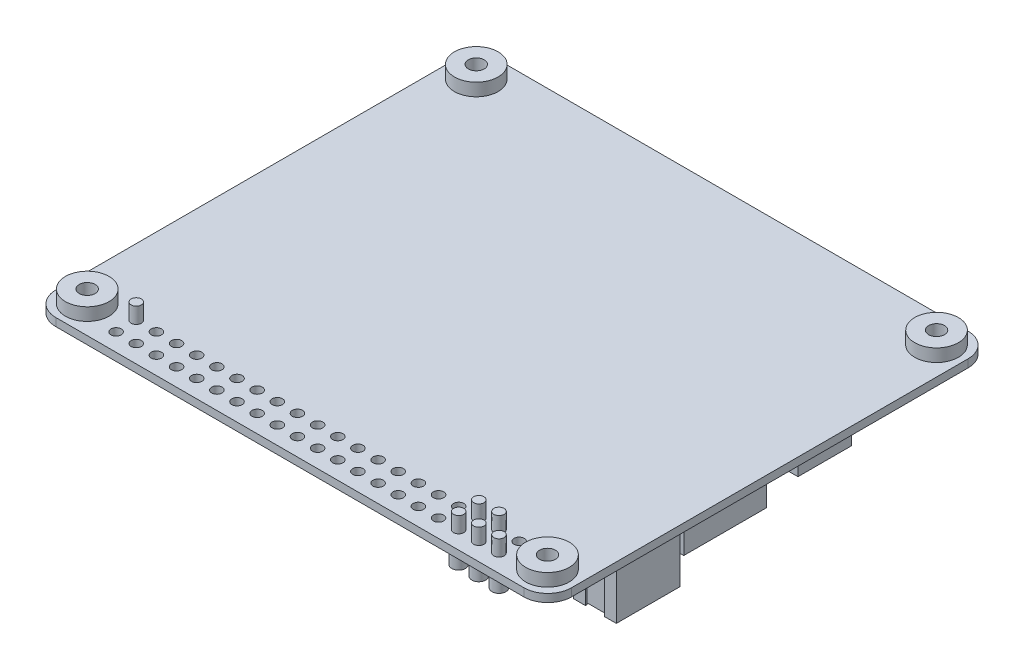
SolidWorks part; units mm, degrees
ref_plane "前视基准面" through (0, 0, 0) normal (0, 0, 1) x (1, 0, 0)
ref_plane "上视基准面" through (0, 0, 0) normal (0, 1, 0) x (1, 0, 0)
ref_plane "右视基准面" through (0, 0, 0) normal (1, 0, 0) x (0, 0, -1)
sketch "草图1" plane through (0, 0, 0) normal (0, 1, 0) x (1, 0, 0)
  line L1 (32.5, -28) -> (-32.5, -28)
  line L2 (32.5, -28) -> (32.5, 28)
  line L3 (32.5, 28) -> (-32.5, 28)
  line L4 (-32.5, -28) -> (-32.5, 28)
  line L5 (32.5, -28) -> (-32.5, 28) construction
  line L6 (32.5, 28) -> (-32.5, -28) construction
  point P0 (0, 0)
  dimension "D1" = 56
  dimension "D2" = 65
extrude "凸台-拉伸1" add sketch "草图1" along normal blind 1
fillet "圆角1" radius 3 4 edges at (32.5, 0.5, -28) (32.5, 0.5, 28) (-32.5, 0.5, 28) (-32.5, 0.5, -28)
sketch "草图2" plane through (0, 1, 0) normal (0, 1, 0) x (1, 0, 0)
  circle A0 centre (-29.0307, 24.5287) radius 2.75
  circle A1 centre (28.9808, 24.5287) radius 2.75
  circle A2 centre (-29.0307, -24.5065) radius 2.75
  circle A3 centre (28.9808, -24.5065) radius 2.75
  dimension "D1" = 5.5
extrude "凸台-拉伸2" add sketch "草图2" along normal blind 1.6
sketch "草图3" plane through (0, 2.6, 0) normal (0, 1, 0) x (1, 0, 0)
  circle A0 centre (-29.0307, 24.5287) radius 1
  circle A1 centre (28.9808, 24.5287) radius 1
  circle A2 centre (-29.0307, -24.5065) radius 1
  circle A3 centre (28.9808, -24.5065) radius 1
  dimension "D1" = 2
extrude "切除-拉伸1" cut sketch "草图3" against normal up to next
sketch "草图4" plane through (0, 0, 0) normal (0, -1, 0) x (1, 0, 0)
  line L0 (29.5, -28) -> (-29.5, -28) construction
  line L1 (25.5, -28) -> (16.5, -28)
  line L2 (25.5, -28) -> (25.5, -20.6)
  line L3 (25.5, -20.6) -> (16.5, -20.6)
  line L4 (16.5, -28) -> (16.5, -20.6)
  line L5 (32.5, 25) -> (32.5, -25) construction
  dimension "D1" = 7.4
  dimension "D2" = 9
  dimension "D3" = 7
extrude "凸台-拉伸3" add sketch "草图4" along normal blind 3.2
sketch "草图5" plane through (0, 0, -28) normal (0, 0, -1) x (-1, 0, 0)
  line L0 (-29.5, 0) -> (-25.5, 0) construction
  line L1 (-16.5, -3.2) -> (-25.5, -3.2)
  line L2 (-16.5, -3.2) -> (-16.5, 0)
  line L3 (-16.5, 0) -> (-25.5, 0)
  line L4 (-25.5, -3.2) -> (-25.5, 0)
  line L5 (-25.5, -3.2) -> (-25.5, 0) construction
extrude "凸台-拉伸4" add sketch "草图5" along normal blind 1
fillet "圆角3" radius 1 4 edges at (25.5, 0, -28.5) (25.5, -3.2, -24.8) (16.5, -3.2, -24.8) (16.5, 0, -28.5)
sketch "草图6" plane through (0, 0, 0) normal (0, -1, 0) x (1, 0, 0)
  line L0 (-32.5, -25) -> (-32.5, 25) construction
  circle A0 centre (-17.5, 0) radius 7
  dimension "D1" = 14
  dimension "D2" = 15
extrude "凸台-拉伸5" add sketch "草图6" along normal blind 2
sketch "草图8" plane through (0, 0, 0) normal (0, -1, 0) x (1, 0, 0)
  circle A0 centre (28.9808, 24.5065) radius 2
  circle A1 centre (28.9808, -24.5287) radius 2
  circle A2 centre (-29.0307, -24.5287) radius 2
  circle A3 centre (-29.0307, 24.5065) radius 2
  dimension "D1" = 4
extrude "凸台-拉伸6" add sketch "草图8" along normal blind 0.5
sketch "草图9" plane through (0, 0, 0) normal (0, 1, 0) x (1, 0, 0)
  circle A0 centre (-29.0307, 24.5287) radius 1
  circle A1 centre (28.9808, 24.5287) radius 1
  circle A2 centre (-29.0307, -24.5065) radius 1
  circle A3 centre (28.9808, -24.5065) radius 1
  circle A4 centre (28.9808, -24.5065) radius 2 construction
  circle A5 centre (28.9808, 24.5287) radius 2 construction
  circle A6 centre (-29.0307, -24.5065) radius 2 construction
  circle A7 centre (-29.0307, 24.5287) radius 2 construction
extrude "切除-拉伸2" cut sketch "草图9" against normal up to next
sketch "草图10" plane through (0, 0, -29) normal (0, 0, -1) x (-1, 0, 0)
  line L8 (-17.5, -0.2) -> (-24.5, -0.2)
  line L9 (-25.3, -1) -> (-25.3, -2.2)
  line L10 (-24.5, -3) -> (-17.5, -3)
  line L11 (-16.7, -2.2) -> (-16.7, -1)
  line L12 (-17.5, -0.2) -> (-24.5, -0.2)
  line L13 (-25.3, -1) -> (-25.3, -2.2)
  line L14 (-24.5, -3) -> (-17.5, -3)
  line L15 (-16.7, -2.2) -> (-16.7, -1)
  arc A8 (-24.5, -0.2) -> (-25.3, -1) centre (-24.5, -1) ccw
  arc A9 (-25.3, -2.2) -> (-24.5, -3) centre (-24.5, -2.2) ccw
  arc A10 (-17.5, -3) -> (-16.7, -2.2) centre (-17.5, -2.2) ccw
  arc A11 (-16.7, -1) -> (-17.5, -0.2) centre (-17.5, -1) ccw
  arc A12 (-24.5, -0.2) -> (-25.3, -1) centre (-24.5, -1) ccw
  arc A13 (-25.3, -2.2) -> (-24.5, -3) centre (-24.5, -2.2) ccw
  arc A14 (-17.5, -3) -> (-16.7, -2.2) centre (-17.5, -2.2) ccw
  arc A15 (-16.7, -1) -> (-17.5, -0.2) centre (-17.5, -1) ccw
  dimension "D1" = 0.2
extrude "切除-拉伸3" cut sketch "草图10" against normal blind 8
sketch "草图12" plane through (0, 0, 0) normal (0, -1, 0) x (1, 0, 0)
  line L0 (16.5, -28) -> (-29.5, -28) construction
  line L1 (-16.6, -28) -> (-23.9, -28)
  line L2 (-16.6, -28) -> (-16.6, -22.7)
  line L3 (-16.6, -22.7) -> (-23.9, -22.7)
  line L4 (-23.9, -28) -> (-23.9, -22.7)
  line L5 (-32.5, -25) -> (-32.5, 25) construction
  dimension "D1" = 7.3
  dimension "D2" = 8.6
  dimension "D3" = 5.3
extrude "凸台-拉伸8" add sketch "草图12" along normal blind 2.4
sketch "草图13" plane through (0, 0, -28) normal (0, 0, -1) x (-1, 0, 0)
  line L1 (23.9, -2.4) -> (16.6, -2.4)
  line L2 (23.9, -2.4) -> (23.9, 0)
  line L3 (23.9, 0) -> (16.6, 0)
  line L4 (16.6, -2.4) -> (16.6, 0)
extrude "凸台-拉伸9" add sketch "草图13" along normal up to surface (1 mm away) up to face at (21, -1.6, -29)
chamfer "倒角1" distance 0.4 angle 45 2 edges at (-16.6, -2.4, -25.85) (-23.9, -2.4, -25.85)
chamfer "倒角2" distance 1 angle 45 2 edges at (-16.6, 0, -28.5) (-23.9, 0, -28.5)
sketch "草图14" plane through (0, 0, -29) normal (0, 0, -1) x (-1, 0, 0)
  line L16 (22.8172, -0.2) -> (17.6828, -0.2)
  line L17 (17.6828, -0.2) -> (16.8, -1.0828)
  line L18 (16.8, -1.0828) -> (16.8, -1.9172)
  line L19 (16.8, -1.9172) -> (17.0828, -2.2)
  line L20 (17.0828, -2.2) -> (23.4172, -2.2)
  line L21 (23.4172, -2.2) -> (23.7, -1.9172)
  line L22 (23.7, -1.9172) -> (23.7, -1.0828)
  line L23 (23.7, -1.0828) -> (22.8172, -0.2)
  line L24 (22.8172, -0.2) -> (17.6828, -0.2)
  line L25 (17.6828, -0.2) -> (16.8, -1.0828)
  line L26 (16.8, -1.0828) -> (16.8, -1.9172)
  line L27 (16.8, -1.9172) -> (17.0828, -2.2)
  line L28 (17.0828, -2.2) -> (23.4172, -2.2)
  line L29 (23.4172, -2.2) -> (23.7, -1.9172)
  line L30 (23.7, -1.9172) -> (23.7, -1.0828)
  line L31 (23.7, -1.0828) -> (22.8172, -0.2)
  dimension "D1" = 0.2
extrude "切除-拉伸4" cut sketch "草图14" against normal blind 2.4
sketch "草图17" plane through (0, 0, -28) normal (0, 0, -1) x (-1, 0, 0)
  line L0 (23.9, -1) -> (23.9, 0)
  line L1 (23.9, 0) -> (22.9, 0)
  line L2 (22.9, 0) -> (23.9, -1)
  line L3 (16.6, 0) -> (17.6, 0)
  line L4 (17.6, 0) -> (16.6, -1)
  line L5 (16.6, -1) -> (16.6, 0) construction
  line L6 (16.6, -1) -> (16.6, 0)
extrude "切除-拉伸5" cut sketch "草图17" against normal up to surface (5.3 mm away) up to face at (-20.25, -1.4667, -22.7)
fillet "圆角4" radius 0.2 1 edges at (-17.5, -2, -7)
sketch "草图19" plane through (0, 0, 0) normal (0, -1, 0) x (1, 0, 0)
  line L0 (32.5, 25) -> (32.5, -25) construction
  line L1 (32, 18.85) -> (26.6, 18.85)
  line L2 (32, 18.85) -> (32, 10.85)
  line L3 (32, 10.85) -> (26.6, 10.85)
  line L4 (26.6, 18.85) -> (26.6, 10.85)
  line L5 (-29.5, 28) -> (29.5, 28) construction
  dimension "D1" = 8
  dimension "D2" = 5.4
  dimension "D3" = 0.5
  dimension "D4" = 9.15
extrude "凸台-拉伸13" add sketch "草图19" along normal blind 6.22
sketch "草图20" plane through (0, -6.22, 0) normal (0, -1, 0) x (1, 0, 0)
  line L0 (30.5, 18.85) -> (30.5, 18.65)
  line L1 (32, 18.85) -> (26.6, 18.85) construction
  line L2 (30.5, 18.65) -> (31.3599, 18.65)
  line L3 (31.3599, 18.65) -> (31.3599, 18.45)
  line L4 (31.3599, 18.45) -> (26.9378, 18.45)
  line L5 (26.9378, 18.45) -> (26.9378, 18.65)
  line L6 (26.9378, 18.65) -> (28.1, 18.65)
  line L7 (28.1, 18.65) -> (28.1, 18.85)
  line L8 (32, 18.85) -> (26.6, 18.85) construction
  line L9 (28.1, 18.85) -> (30.5, 18.85)
  line L10 (30.5, 10.85) -> (30.5, 11.05)
  line L11 (26.6, 10.85) -> (32, 10.85) construction
  line L12 (30.5, 11.05) -> (31.3599, 11.05)
  line L13 (31.3599, 11.05) -> (31.3599, 11.25)
  line L14 (31.3599, 11.25) -> (26.9378, 11.25)
  line L15 (26.9378, 11.25) -> (26.9378, 11.05)
  line L16 (26.9378, 11.05) -> (28.1, 11.05)
  line L17 (28.1, 11.05) -> (28.1, 10.85)
  line L18 (28.1, 10.85) -> (30.5, 10.85)
  line L19 (32, 10.85) -> (32, 18.85) construction
  line L20 (26.6, 18.85) -> (26.6, 10.85) construction
  dimension "D1" = 0.2
  dimension "D2" = 0.2
  dimension "D3" = 0.2
  dimension "D4" = 1.5
  dimension "D5" = 1.5
extrude "切除-拉伸6" cut sketch "草图20" against normal blind 6.22
sketch "草图21" plane through (0, -6.22, 0) normal (0, -1, 0) x (1, 0, 0)
  line L1 (31.3599, 18.0753) -> (26.9378, 18.0753)
  line L2 (31.3599, 18.0753) -> (31.3599, 11.6247)
  line L3 (31.3599, 11.6247) -> (26.9378, 11.6247)
  line L4 (26.9378, 18.0753) -> (26.9378, 11.6247)
  line L5 (31.3599, 18.0753) -> (26.9378, 11.6247) construction
  line L6 (31.3599, 11.6247) -> (26.9378, 18.0753) construction
  point P0 (29.1489, 14.85)
extrude "切除-拉伸7" cut sketch "草图21" against normal blind 5
sketch "草图22" plane through (0, -1.22, 0) normal (0, -1, 0) x (1, 0, 0)
  line L1 (29.5742, 16.0721) -> (29.0742, 16.0721)
  line L2 (29.5742, 16.0721) -> (29.5742, 15.5721)
  line L3 (29.5742, 15.5721) -> (29.0742, 15.5721)
  line L4 (29.0742, 16.0721) -> (29.0742, 15.5721)
  line L5 (29.5742, 16.0721) -> (29.0742, 15.5721) construction
  line L6 (29.5742, 15.5721) -> (29.0742, 16.0721) construction
  line L7 (29.5566, 14.331) -> (29.0566, 14.331)
  line L8 (29.5566, 14.331) -> (29.5566, 13.831)
  line L9 (29.5566, 13.831) -> (29.0566, 13.831)
  line L10 (29.0566, 14.331) -> (29.0566, 13.831)
  line L11 (29.5566, 14.331) -> (29.0566, 13.831) construction
  line L12 (29.5566, 13.831) -> (29.0566, 14.331) construction
  point P0 (29.3242, 15.8221)
  point P5 (29.3066, 14.081)
  dimension "D1" = 0.5
extrude "凸台-拉伸14" add sketch "草图22" along normal blind 5
chamfer "倒角3" distance 0.1 angle 45 8 edges at (29.3066, -6.22, 14.331) (29.5566, -6.22, 14.081) (29.3066, -6.22, 13.831) (29.0566, -6.22, 14.081) (29.3242, -6.22, 16.0721) (29.5742, -6.22, 15.8221) (29.3242, -6.22, 15.5721) (29.0742, -6.22, 15.8221)
sketch "草图26" plane through (0, 0, 0) normal (0, -1, 0) x (1, 0, 0)
  circle A0 centre (24.13, 25.77) radius 0.65
  circle A40 centre (21.59, 25.77) radius 0.65
  circle A41 centre (19.05, 25.77) radius 0.65
  circle A42 centre (16.51, 25.77) radius 0.65
  circle A43 centre (13.97, 25.77) radius 0.65
  circle A44 centre (11.43, 25.77) radius 0.65
  circle A45 centre (8.89, 25.77) radius 0.65
  circle A46 centre (6.35, 25.77) radius 0.65
  circle A47 centre (3.81, 25.77) radius 0.65
  circle A48 centre (1.27, 25.77) radius 0.65
  circle A49 centre (-1.27, 25.77) radius 0.65
  circle A50 centre (-3.81, 25.77) radius 0.65
  circle A51 centre (-6.35, 25.77) radius 0.65
  circle A52 centre (-8.89, 25.77) radius 0.65
  circle A53 centre (-11.43, 25.77) radius 0.65
  circle A54 centre (-13.97, 25.77) radius 0.65
  circle A55 centre (-16.51, 25.77) radius 0.65
  circle A56 centre (-19.05, 25.77) radius 0.65
  circle A57 centre (-21.59, 25.77) radius 0.65
  circle A58 centre (-24.13, 25.77) radius 0.65
  circle A59 centre (21.59, 23.23) radius 0.65
  circle A60 centre (19.05, 23.23) radius 0.65
  circle A61 centre (16.51, 23.23) radius 0.65
  circle A62 centre (13.97, 23.23) radius 0.65
  circle A63 centre (11.43, 23.23) radius 0.65
  circle A64 centre (8.89, 23.23) radius 0.65
  circle A65 centre (6.35, 23.23) radius 0.65
  circle A66 centre (3.81, 23.23) radius 0.65
  circle A67 centre (1.27, 23.23) radius 0.65
  circle A68 centre (-1.27, 23.23) radius 0.65
  circle A69 centre (-3.81, 23.23) radius 0.65
  circle A70 centre (-6.35, 23.23) radius 0.65
  circle A71 centre (-8.89, 23.23) radius 0.65
  circle A72 centre (-11.43, 23.23) radius 0.65
  circle A73 centre (-13.97, 23.23) radius 0.65
  circle A74 centre (-16.51, 23.23) radius 0.65
  circle A75 centre (-19.05, 23.23) radius 0.65
  circle A76 centre (-21.59, 23.23) radius 0.65
  circle A77 centre (-24.13, 23.23) radius 0.65
  circle A78 centre (24.13, 23.23) radius 0.65
  dimension "D1" = 1.3
  dimension "D2" = 20
  dimension "D3" = 2
extrude "切除-拉伸8" cut sketch "草图26" against normal up to surface (1 mm away) up to face at (28.9808, 1, 27.2565)
sketch "草图27" plane through (0, 0, 0) normal (0, -1, 0) x (1, 0, 0)
  circle A0 centre (24.13, 25.77) radius 1.15
  circle A1 centre (21.59, 25.77) radius 1.15
  circle A2 centre (21.59, 23.23) radius 1.15
  circle A3 centre (19.05, 25.77) radius 1.15
  circle A4 centre (19.05, 23.23) radius 1.15
  circle A5 centre (13.97, 23.23) radius 1.15
  circle A6 centre (21.59, 25.77) radius 0.65 construction
  dimension "D1" = 2.3
extrude "凸台-拉伸18" add sketch "草图27" along normal blind 0.8
sketch "草图28" plane through (0, -0.8, 0) normal (0, -1, 0) x (-1, 0, 0)
  circle A0 centre (-24.13, -25.77) radius 0.875
  circle A1 centre (-21.59, -25.77) radius 0.875
  circle A2 centre (-19.05, -23.23) radius 0.875
  circle A3 centre (-21.59, -23.23) radius 0.875
  circle A4 centre (-19.05, -25.77) radius 0.875
  circle A5 centre (-13.97, -23.23) radius 0.875
  dimension "D1" = 1.75
extrude "凸台-拉伸19" add sketch "草图28" along normal blind 2
sketch "草图29" plane through (0, 0, 0) normal (0, 1, 0) x (1, 0, 0)
  circle A0 centre (19.05, -23.23) radius 0.65 construction
  circle A1 centre (19.05, -25.77) radius 0.65 construction
  circle A2 centre (21.59, -23.23) radius 0.65 construction
  circle A4 centre (24.13, -25.77) radius 0.65 construction
  circle A5 centre (-24.13, -23.23) radius 0.65 construction
  circle A6 centre (19.05, -23.23) radius 0.65
  circle A7 centre (19.05, -25.77) radius 0.65
  circle A8 centre (21.59, -23.23) radius 0.65
  circle A9 centre (21.59, -25.77) radius 0.65
  circle A10 centre (24.13, -25.77) radius 0.65
  circle A11 centre (-24.13, -23.23) radius 0.65
  circle A12 centre (21.59, -25.77) radius 0.65 construction
extrude "凸台-拉伸20" add sketch "草图29" along normal blind 3
sketch "草图30" plane through (0, 0, -28) normal (0, 0, -1) x (-1, 0, 0)
  line L0 (-16.5, 0) -> (-17.5, 0)
  line L1 (-16.5, 0) -> (-16.5, -1) construction
  line L2 (-16.5, 0) -> (-16.5, -1)
  line L3 (-25.5, 0) -> (-24.5, 0)
  line L4 (-25.5, -1) -> (-25.5, 0) construction
  line L5 (-25.5, -1) -> (-25.5, 0)
  arc A0 (-16.5, -1) -> (-17.5, 0) centre (-17.5, -1) ccw construction
  arc A1 (-16.5, -1) -> (-17.5, 0) centre (-17.5, -1) ccw
  arc A2 (-24.5, 0) -> (-25.5, -1) centre (-24.5, -1) ccw construction
  arc A3 (-24.5, 0) -> (-25.5, -1) centre (-24.5, -1) ccw
extrude "切除-拉伸9" cut sketch "草图30" against normal up to next
sketch "草图31" plane through (0, 0, 0) normal (0, -1, 0) x (1, 0, 0)
  line L0 (-269.1222, 141.019) -> (182.8778, 141.019) construction
  line L1 (24.5, -20.6) -> (17.5, -20.6) construction
  line L2 (31.459, 9.8102) -> (19.8345, 9.8102)
  line L3 (31.459, 9.8102) -> (31.459, -0.6109)
  line L4 (31.459, -0.6109) -> (19.8345, -0.6109)
  line L5 (19.8345, 9.8102) -> (19.8345, -0.6109)
  line L6 (31.459, -1.1785) -> (28.1669, -1.1785)
  line L7 (31.459, -1.1785) -> (31.459, -4.516)
  line L8 (31.459, -4.516) -> (28.1669, -4.516)
  line L9 (28.1669, -1.1785) -> (28.1669, -4.516)
  line L10 (27.1452, -1.4056) -> (22.332, -1.4056)
  line L11 (27.1452, -1.4056) -> (27.1452, -4.1981)
  line L12 (27.1452, -4.1981) -> (22.332, -4.1981)
  line L13 (22.332, -1.4056) -> (22.332, -4.1981)
  line L14 (31.0503, -4.9928) -> (23.558, -4.9928)
  line L15 (31.0503, -4.9928) -> (31.0503, -11.7586)
  line L16 (31.0503, -11.7586) -> (23.558, -11.7586)
  line L17 (23.558, -4.9928) -> (23.558, -11.7586)
  line L18 (31.459, -13.2884) -> (30.0812, -13.2884)
  line L19 (31.459, -13.2884) -> (31.459, -15.1195)
  line L20 (31.459, -15.1195) -> (30.0812, -15.1195)
  line L21 (30.0812, -13.2884) -> (30.0812, -15.1195)
  line L22 (29.3946, -12.2203) -> (27.6398, -12.2203)
  line L23 (29.3946, -12.2203) -> (29.3946, -13.0596)
  line L24 (29.3946, -13.0596) -> (27.6398, -13.0596)
  line L25 (27.6398, -12.2203) -> (27.6398, -13.0596)
  line L26 (25.1221, -19.2775) -> (23.024, -19.2775)
  line L27 (25.1221, -19.2775) -> (25.1221, -20.6)
  line L28 (25.1221, -20.6) -> (23.024, -20.6)
  line L29 (23.024, -19.2775) -> (23.024, -20.6)
  line L30 (24.5, -20.6) -> (17.5, -20.6) construction
  line L31 (21.8033, -19.2775) -> (20.7352, -19.2775)
  line L32 (21.8033, -19.2775) -> (21.8033, -20.6)
  line L33 (21.8033, -20.6) -> (20.7352, -20.6)
  line L34 (20.7352, -19.2775) -> (20.7352, -20.6)
  line L35 (-4.9095, -24.5987) -> (-6.2095, -24.5987)
  line L36 (20.2393, -19.2775) -> (19.2474, -19.2775)
  line L37 (20.2393, -19.2775) -> (20.2393, -20.6)
  line L38 (20.2393, -20.6) -> (19.2474, -20.6)
  line L39 (19.2474, -19.2775) -> (19.2474, -20.6)
  line L40 (25.1221, -17.065) -> (23.024, -17.065)
  line L41 (25.1221, -17.065) -> (25.1221, -18.5146)
  line L42 (25.1221, -18.5146) -> (23.024, -18.5146)
  line L43 (23.024, -17.065) -> (23.024, -18.5146)
  line L44 (21.2692, -13.0596) -> (18.103, -13.0596)
  line L45 (21.2692, -13.0596) -> (21.2692, -16.3402)
  line L46 (21.2692, -16.3402) -> (18.103, -16.3402)
  line L47 (18.103, -13.0596) -> (18.103, -16.3402)
  line L48 (19.2474, -0.6109) -> (18.4047, -0.6109)
  line L49 (19.2474, -0.6109) -> (19.2474, -2.216)
  line L50 (19.2474, -2.216) -> (18.4047, -2.216)
  line L51 (18.4047, -0.6109) -> (18.4047, -2.216)
  line L52 (13.1588, -24.973) -> (8.3931, -24.973)
  line L53 (13.1588, -24.973) -> (13.1588, -27.3005)
  line L54 (13.1588, -27.3005) -> (8.3931, -27.3005)
  line L55 (8.3931, -24.973) -> (8.3931, -27.3005)
  line L56 (4.6988, -24.973) -> (0, -24.973)
  line L57 (4.6988, -24.973) -> (4.6988, -27.3005)
  line L58 (4.6988, -27.3005) -> (0, -27.3005)
  line L59 (0, -24.973) -> (0, -27.3005)
  line L60 (8.3931, 15.9758) -> (4.9221, 15.9758)
  line L61 (8.3931, 15.9758) -> (8.3931, 13.2491)
  line L62 (8.3931, 13.2491) -> (4.9221, 13.2491)
  line L63 (4.9221, 15.9758) -> (4.9221, 13.2491)
  line L64 (8.3931, 11.7221) -> (4.9221, 11.7221)
  line L65 (8.3931, 11.7221) -> (8.3931, 9.0318)
  line L66 (8.3931, 9.0318) -> (4.9221, 9.0318)
  line L67 (4.9221, 11.7221) -> (4.9221, 9.0318)
  line L68 (9.6847, 6.3051) -> (5.9037, 6.3051)
  line L69 (9.6847, 6.3051) -> (9.6847, 1.4698)
  line L70 (9.6847, 1.4698) -> (5.9037, 1.4698)
  line L71 (5.9037, 6.3051) -> (5.9037, 1.4698)
  line L80 (-1.5572, -24.1659) -> (-3.3676, -24.1659)
  line L81 (-1.5572, -24.1659) -> (-1.5572, -27.3005)
  line L82 (-1.5572, -27.3005) -> (-3.3676, -27.3005)
  line L83 (-3.3676, -24.1659) -> (-3.3676, -27.3005)
  line L88 (-4.9095, -24.5987) -> (-4.9095, -26.7453)
  line L89 (-4.9095, -26.7453) -> (-6.2095, -26.7453)
  line L90 (-6.2095, -24.5987) -> (-6.2095, -26.7453)
  line L92 (-7.0018, -24.5987) -> (-8.3018, -24.5987)
  line L93 (-7.0018, -24.5987) -> (-7.0018, -26.7453)
  line L94 (-7.0018, -26.7453) -> (-8.3018, -26.7453)
  line L95 (-8.3018, -24.5987) -> (-8.3018, -26.7453)
  line L96 (-9.1473, -24.5987) -> (-10.4473, -24.5987)
  line L97 (-9.1473, -24.5987) -> (-9.1473, -26.7453)
  line L98 (-9.1473, -26.7453) -> (-10.4473, -26.7453)
  line L99 (-10.4473, -24.5987) -> (-10.4473, -26.7453)
  line L100 (-11.2125, -24.5987) -> (-12.5125, -24.5987)
  line L101 (-11.2125, -24.5987) -> (-11.2125, -26.7453)
  line L102 (-11.2125, -26.7453) -> (-12.5125, -26.7453)
  line L103 (-12.5125, -24.5987) -> (-12.5125, -26.7453)
  line L104 (-13.2578, -24.5987) -> (-14.5578, -24.5987)
  line L105 (-13.2578, -24.5987) -> (-13.2578, -26.7453)
  line L106 (-13.2578, -26.7453) -> (-14.5578, -26.7453)
  line L107 (-14.5578, -24.5987) -> (-14.5578, -26.7453)
  line L108 (0.6545, -17.8156) -> (-0.8398, -17.8156)
  line L109 (0.6545, -17.8156) -> (0.6545, -19.6835)
  line L110 (0.6545, -19.6835) -> (-0.8398, -19.6835)
  line L111 (-0.8398, -17.8156) -> (-0.8398, -19.6835)
  line L112 (-9.9754, -18.0873) -> (-11.6734, -18.0873)
  line L113 (-9.9754, -18.0873) -> (-9.9754, -18.9703)
  line L114 (-9.9754, -18.9703) -> (-11.6734, -18.9703)
  line L115 (-11.6734, -18.0873) -> (-11.6734, -18.9703)
  line L116 (-1.2233, 3.594) -> (-2.668, 3.594)
  line L117 (-1.2233, 3.594) -> (-1.2233, 1.8282)
  line L118 (-1.2233, 1.8282) -> (-2.668, 1.8282)
  line L119 (-2.668, 3.594) -> (-2.668, 1.8282)
  line L120 (-2.2552, -2.7581) -> (-3.1725, -2.7581)
  line L121 (-2.2552, -2.7581) -> (-2.2552, -4.516)
  line L122 (-2.2552, -4.516) -> (-3.1725, -4.516)
  line L123 (-3.1725, -2.7581) -> (-3.1725, -4.516)
  line L124 (-4.6401, -2.7581) -> (-5.5344, -2.7581)
  line L125 (-4.6401, -2.7581) -> (-4.6401, -4.516)
  line L126 (-4.6401, -4.516) -> (-5.5344, -4.516)
  line L127 (-5.5344, -2.7581) -> (-5.5344, -4.516)
  line L128 (-6.2095, -3.8955) -> (-7.2269, -3.8955)
  line L129 (-6.2095, -3.8955) -> (-6.2095, -5.7277)
  line L130 (-6.2095, -5.7277) -> (-7.2269, -5.7277)
  line L131 (-7.2269, -3.8955) -> (-7.2269, -5.7277)
  line L132 (-7.6341, -3.8955) -> (-8.5039, -3.8955)
  line L133 (-7.6341, -3.8955) -> (-7.6341, -5.7277)
  line L134 (-7.6341, -5.7277) -> (-8.5039, -5.7277)
  line L135 (-8.5039, -3.8955) -> (-8.5039, -5.7277)
  line L136 (-8.8925, -3.8955) -> (-9.8179, -3.8955)
  line L137 (-8.8925, -3.8955) -> (-8.8925, -5.7277)
  line L138 (-8.8925, -5.7277) -> (-9.8179, -5.7277)
  line L139 (-9.8179, -3.8955) -> (-9.8179, -5.7277)
  line L140 (-10.188, -3.8955) -> (-11.2125, -3.8955)
  line L141 (-10.188, -3.8955) -> (-10.188, -5.7277)
  line L142 (-10.188, -5.7277) -> (-11.2125, -5.7277)
  line L143 (-11.2125, -3.8955) -> (-11.2125, -5.7277)
  line L144 (12.5814, 9.3712) -> (10.7759, 9.3712)
  line L145 (12.5814, 9.3712) -> (12.5814, 8.2563)
  line L146 (12.5814, 8.2563) -> (10.7759, 8.2563)
  line L147 (10.7759, 9.3712) -> (10.7759, 8.2563)
  line L148 (11.6787, 7.8846) -> (10.0309, 7.8846)
  line L149 (11.6787, 7.8846) -> (11.6787, 6.9555)
  line L150 (11.6787, 6.9555) -> (10.0309, 6.9555)
  line L151 (10.0309, 7.8846) -> (10.0309, 6.9555)
  line L152 (12.1492, 6.3051) -> (10.4025, 6.3051)
  line L153 (12.1492, 6.3051) -> (12.1492, 5.2831)
  line L154 (12.1492, 5.2831) -> (10.4025, 5.2831)
  line L155 (10.4025, 6.3051) -> (10.4025, 5.2831)
  line L156 (12.1492, 1.4698) -> (10.4025, 1.4698)
  line L157 (12.1492, 1.4698) -> (12.1492, 0.5632)
  line L158 (12.1492, 0.5632) -> (10.4025, 0.5632)
  line L159 (10.4025, 1.4698) -> (10.4025, 0.5632)
  line L160 (11.6787, -0.3659) -> (10.4025, -0.3659)
  line L161 (11.6787, -0.3659) -> (11.6787, -2.216)
  line L162 (11.6787, -2.216) -> (10.4025, -2.216)
  line L163 (10.4025, -0.3659) -> (10.4025, -2.216)
  line L164 (10.0309, -0.3659) -> (8.9159, -0.3659)
  line L165 (10.0309, -0.3659) -> (10.0309, -2.216)
  line L166 (10.0309, -2.216) -> (8.9159, -2.216)
  line L167 (8.9159, -0.3659) -> (8.9159, -2.216)
  line L168 (8.9159, 7.8846) -> (7.2064, 7.8846)
  line L169 (8.9159, 7.8846) -> (8.9159, 6.9555)
  line L170 (8.9159, 6.9555) -> (7.2064, 6.9555)
  line L171 (7.2064, 7.8846) -> (7.2064, 6.9555)
  line L172 (6.5746, 0.5632) -> (5.6083, 0.5632)
  line L173 (6.5746, 0.5632) -> (6.5746, -0.9234)
  line L174 (6.5746, -0.9234) -> (5.6083, -0.9234)
  line L175 (5.6083, 0.5632) -> (5.6083, -0.9234)
  line L176 (4.9221, 1.8282) -> (3.1926, 1.8282)
  line L177 (4.9221, 1.8282) -> (4.9221, 1.0165)
  line L178 (4.9221, 1.0165) -> (3.1926, 1.0165)
  line L179 (3.1926, 1.8282) -> (3.1926, 1.0165)
  line L180 (4.9221, 0.2287) -> (4.0574, 0.2287)
  line L181 (4.9221, 0.2287) -> (4.9221, -1.4056)
  line L182 (4.9221, -1.4056) -> (4.0574, -1.4056)
  line L183 (4.0574, 0.2287) -> (4.0574, -1.4056)
  line L184 (3.6386, 0.2287) -> (2.7466, 0.2287)
  line L185 (3.6386, 0.2287) -> (3.6386, -1.4056)
  line L186 (3.6386, -1.4056) -> (2.7466, -1.4056)
  line L187 (2.7466, 0.2287) -> (2.7466, -1.4056)
  line L188 (5.3755, 3.0635) -> (4.4942, 3.0635)
  line L189 (5.3755, 3.0635) -> (5.3755, 4.8142)
  line L190 (1.6317, 2.3471) -> (3.1926, 2.3471)
  line L191 (1.6317, 2.3471) -> (1.6317, 3.3134)
  line L192 (1.6317, 3.3134) -> (3.1926, 3.3134)
  line L193 (3.1926, 2.3471) -> (3.1926, 3.3134)
  line L194 (5.3755, 4.8142) -> (4.4942, 4.8142)
  line L195 (4.4942, 3.0635) -> (4.4942, 4.8142)
  line L196 (-26.4365, 18.1309) -> (-28.123, 18.1309)
  line L197 (-26.4365, 18.1309) -> (-26.4365, 14.8151)
  line L198 (-26.4365, 14.8151) -> (-28.123, 14.8151)
  line L199 (-28.123, 18.1309) -> (-28.123, 14.8151)
  line L200 (-14.8746, -12.2203) -> (-16.6449, -12.2203)
  line L201 (-14.8746, -12.2203) -> (-14.8746, -13.1933)
  line L202 (-14.8746, -13.1933) -> (-16.6449, -13.1933)
  line L203 (-16.6449, -12.2203) -> (-16.6449, -13.1933)
  line L204 (-14.2012, -14.6161) -> (-17.3617, -14.6161)
  line L205 (-14.2012, -14.6161) -> (-14.2012, -16.5384)
  line L206 (-14.2012, -16.5384) -> (-17.3617, -16.5384)
  line L207 (-17.3617, -14.6161) -> (-17.3617, -16.5384)
  line L208 (-17.8504, -16.6905) -> (-18.8061, -16.6905)
  line L209 (-17.8504, -16.6905) -> (-17.8504, -18.363)
  line L210 (-17.8504, -18.363) -> (-18.8061, -18.363)
  line L211 (-18.8061, -16.6905) -> (-18.8061, -18.363)
  line L212 (-19.4653, -16.6905) -> (-20.411, -16.6905)
  line L213 (-19.4653, -16.6905) -> (-19.4653, -18.363)
  line L214 (-19.4653, -18.363) -> (-20.411, -18.363)
  line L215 (-20.411, -16.6905) -> (-20.411, -18.363)
  line L216 (-21.0003, -16.6905) -> (-21.9533, -16.6905)
  line L217 (-21.0003, -16.6905) -> (-21.0003, -18.363)
  line L218 (-21.0003, -18.363) -> (-21.9533, -18.363)
  line L219 (-21.9533, -16.6905) -> (-21.9533, -18.363)
  line L220 (-22.4419, -16.6905) -> (-23.3932, -16.6905)
  line L221 (-22.4419, -16.6905) -> (-22.4419, -18.363)
  line L222 (-22.4419, -18.363) -> (-23.3932, -18.363)
  line L223 (-23.3932, -16.6905) -> (-23.3932, -18.363)
  line L224 (-19.5638, -11.4061) -> (-22.1884, -11.4061)
  line L225 (-19.5638, -11.4061) -> (-19.5638, -14.9023)
  line L226 (-19.5638, -14.9023) -> (-22.1884, -14.9023)
  line L227 (-22.1884, -11.4061) -> (-22.1884, -14.9023)
  dimension "D1" = 1.3
extrude "凸台-拉伸21" add sketch "草图31" along normal blind 0.6
sketch "草图32" plane through (0, -0.6, 0) normal (0, -1, 0) x (1, 0, 0)
  line L4 (31.459, -0.6109) -> (31.459, 9.8102)
  line L5 (31.459, 9.8102) -> (19.8345, 9.8102)
  line L6 (19.8345, 9.8102) -> (19.8345, -0.6109)
  line L7 (19.8345, -0.6109) -> (31.459, -0.6109)
  line L8 (31.459, -0.6109) -> (31.459, 9.8102)
  line L9 (31.459, 9.8102) -> (19.8345, 9.8102)
  line L10 (19.8345, 9.8102) -> (19.8345, -0.6109)
  line L11 (19.8345, -0.6109) -> (31.459, -0.6109)
  dimension "D1" = 0
extrude "凸台-拉伸22" add sketch "草图32" along normal blind 3
sketch "草图33" plane through (0, -0.6, 0) normal (0, -1, 0) x (1, 0, 0)
  line L4 (31.0503, -11.7586) -> (31.0503, -4.9928)
  line L5 (31.0503, -4.9928) -> (23.558, -4.9928)
  line L6 (23.558, -4.9928) -> (23.558, -11.7586)
  line L7 (23.558, -11.7586) -> (31.0503, -11.7586)
  line L8 (31.0503, -11.7586) -> (31.0503, -4.9928)
  line L9 (31.0503, -4.9928) -> (23.558, -4.9928)
  line L10 (23.558, -4.9928) -> (23.558, -11.7586)
  line L11 (23.558, -11.7586) -> (31.0503, -11.7586)
  dimension "D1" = 0
extrude "凸台-拉伸23" add sketch "草图33" along normal blind 2
sketch "草图34" plane through (0, -0.6, 0) normal (0, -1, 0) x (1, 0, 0)
  line L0 (13.1588, -27.3005) -> (13.1588, -24.973) construction
  line L1 (13.1588, -24.973) -> (8.3931, -24.973) construction
  line L2 (8.3931, -24.973) -> (8.3931, -27.3005) construction
  line L3 (8.3931, -27.3005) -> (13.1588, -27.3005) construction
  line L4 (4.6988, -27.3005) -> (4.6988, -24.973) construction
  line L5 (4.6988, -24.973) -> (0, -24.973) construction
  line L6 (0, -24.973) -> (0, -27.3005) construction
  line L7 (0, -27.3005) -> (4.6988, -27.3005) construction
  line L8 (13.1588, -27.3005) -> (13.1588, -24.973)
  line L9 (13.1588, -24.973) -> (8.3931, -24.973)
  line L10 (8.3931, -24.973) -> (8.3931, -27.3005)
  line L11 (8.3931, -27.3005) -> (13.1588, -27.3005)
  line L12 (4.6988, -27.3005) -> (4.6988, -24.973)
  line L13 (4.6988, -24.973) -> (0, -24.973)
  line L14 (0, -24.973) -> (0, -27.3005)
  line L15 (0, -27.3005) -> (4.6988, -27.3005)
extrude "凸台-拉伸24" add sketch "草图34" along normal blind 1
sketch "草图35" plane through (0, 0, -27.3005) normal (0, 0, -1) x (-1, 0, 0)
  line L4 (-8.3931, -1.6) -> (-13.1588, -1.6) construction
  line L5 (-1.1494, -1.3039) -> (-3.5494, -1.3039)
  line L6 (-1.1494, -1.3039) -> (-1.1494, -0.2961)
  line L7 (-1.1494, -0.2961) -> (-3.5494, -0.2961)
  line L8 (-3.5494, -1.3039) -> (-3.5494, -0.2961)
  line L9 (-1.1494, -1.3039) -> (-3.5494, -0.2961) construction
  line L10 (-1.1494, -0.2961) -> (-3.5494, -1.3039) construction
  line L11 (-9.5759, -1.3039) -> (-11.9759, -1.3039)
  line L12 (-9.5759, -1.3039) -> (-9.5759, -0.2961)
  line L13 (-9.5759, -0.2961) -> (-11.9759, -0.2961)
  line L14 (-11.9759, -1.3039) -> (-11.9759, -0.2961)
  line L15 (-9.5759, -1.3039) -> (-11.9759, -0.2961) construction
  line L16 (-9.5759, -0.2961) -> (-11.9759, -1.3039) construction
  line L17 (0, -1.6) -> (-4.6988, -1.6) construction
  point P0 (-10.7759, -0.8)
  point P2 (-2.3494, -0.8)
  point P13 (-10.7759, -1.6)
  point P17 (-2.3494, -1.6)
  dimension "D1" = 2.4
extrude "凸台-拉伸25" add sketch "草图35" along normal blind 0.8
